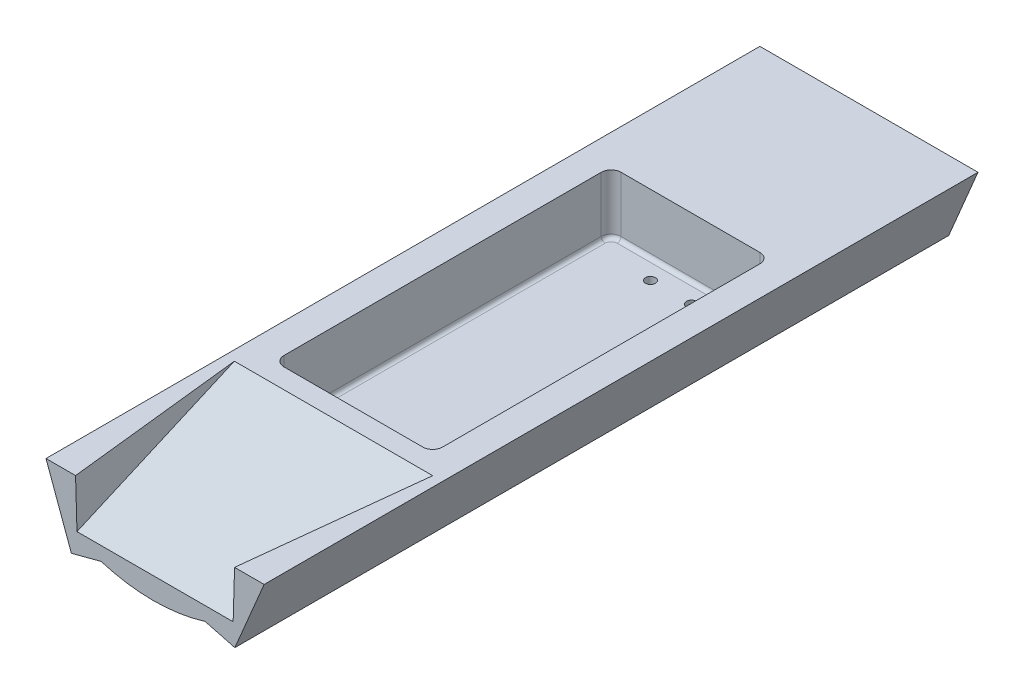
SolidWorks part; units mm, degrees
ref_plane "Front Plane" through (0, 0, 0) normal (0, 0, 1) x (1, 0, 0)
ref_plane "Top Plane" through (0, 0, 0) normal (0, 1, 0) x (1, 0, 0)
ref_plane "Right Plane" through (0, 0, 0) normal (1, 0, 0) x (0, 0, -1)
sketch "Sketch1" plane through (0, 0, 0) normal (0, 0, 1) x (1, 0, 0)
  line L6 (-279.4, 177.8) -> (279.4, 177.8)
  line L9 (0, 0) -> (0, 177.8) construction
  line L15 (-279.4, 177.8) -> (-214.4, 0)
  line L16 (-214.4, 0) -> (-138.2, 20)
  line L18 (204.4, 0) -> (279.4, 177.8)
  line L19 (204.4, 0) -> (128.2, 20)
  arc A0 (-138.2, 20) -> (128.2, 20) centre (-5, 452.931) ccw
  dimension "D1" = 558.8
  dimension "D3" = 177.8
  dimension "D4" = 65
  dimension "D5" = 20
  dimension "D6" = 76.2
  dimension "D7" = 76.2
  dimension "75" = 75
extrude "Boss-Extrude2" add sketch "Sketch1" against normal blind 1828.8
sketch "Sketch2" plane through (0, 177.8, 0) normal (0, 1, 0) x (1, 0, 0)
  line L1 (-203.2, 0) -> (203.2, 0)
  line L3 (-254, 457.2) -> (254, 457.2)
  line L6 (-254, 457.2) -> (-203.2, 0)
  line L7 (254, 457.2) -> (203.2, 0)
  line L8 (279.4, 0) -> (-279.4, 0) construction
  dimension "D1" = 508
  dimension "D2" = 457.2
  dimension "D3" = 50.8
  dimension "D4" = 50.8
ref_plane "Plane1" through (0, 51.5897, 13.8234) normal (0, 0.9659, 0.2588) x (1, 0, 0)
sketch "Sketch7" plane through (0, 51.5897, 13.8234) normal (0, 0.9659, 0.2588) x (1, 0, 0)
  line L1 (-254, 487.6393) -> (254, 487.6393)
  line L2 (-254, 487.6393) -> (-196.5534, -16.2318)
  line L3 (254, 487.6393) -> (196.5534, -16.2318)
  line L6 (-196.5534, -16.2318) -> (196.5534, -16.2318)
  dimension "D1" = 508
extrude "Cut-Extrude2" cut sketch "Sketch7" along normal through all
sketch "Sketch8" plane through (0, 177.8, 0) normal (0, 1, 0) x (1, 0, 0)
  line L0 (-279.4, 1828.8) -> (-279.4, 0) construction
  line L1 (-203.2, 508) -> (203.2, 508)
  line L2 (-203.2, 508) -> (-203.2, 1371.6)
  line L3 (-203.2, 1371.6) -> (203.2, 1371.6)
  line L4 (203.2, 508) -> (203.2, 1371.6)
  line L5 (254, 457.2) -> (-254, 457.2) construction
  dimension "D1" = 406.4
  dimension "D2" = 863.6
  dimension "D3" = 76.2
  dimension "D4" = 50.8
extrude "Cut-Extrude5" cut sketch "Sketch8" against normal blind 152.4
fillet "Fillet1" radius 10 4 edges at (0, 25.4, -1371.6) (203.2, 25.4, -939.8) (0, 25.4, -508) (-203.2, 25.4, -939.8)
fillet "Fillet2" radius 25.4 8 edges at (200.2711, 28.3289, -510.9289) (-200.2711, 28.3289, -510.9289) (-203.2, 106.6, -508) (203.2, 106.6, -508) (-200.2711, 28.3289, -1368.6711) (200.2711, 28.3289, -1368.6711) (203.2, 106.6, -1371.6) (-203.2, 106.6, -1371.6)
sketch "Sketch9" plane through (0, 25.4, 0) normal (0, 1, 0) x (1, 0, 0)
  line L0 (0, 1371.6) -> (0, 508) construction
  line L1 (177.8, 1371.6) -> (-177.8, 1371.6) construction
  line L2 (-177.8, 508) -> (177.8, 508) construction
  circle A0 centre (-52.5, 1321.6) radius 12.7
  circle A1 centre (52.5, 1321.6) radius 12.7
  circle A2 centre (0, 571.6) radius 10
  dimension "D1" = 25.4
  dimension "D3" = 50
  dimension "D4" = 20
  dimension "D5" = 750
  dimension "D2" = 52.5
extrude "Cut-Extrude6" cut sketch "Sketch9" against normal through all
